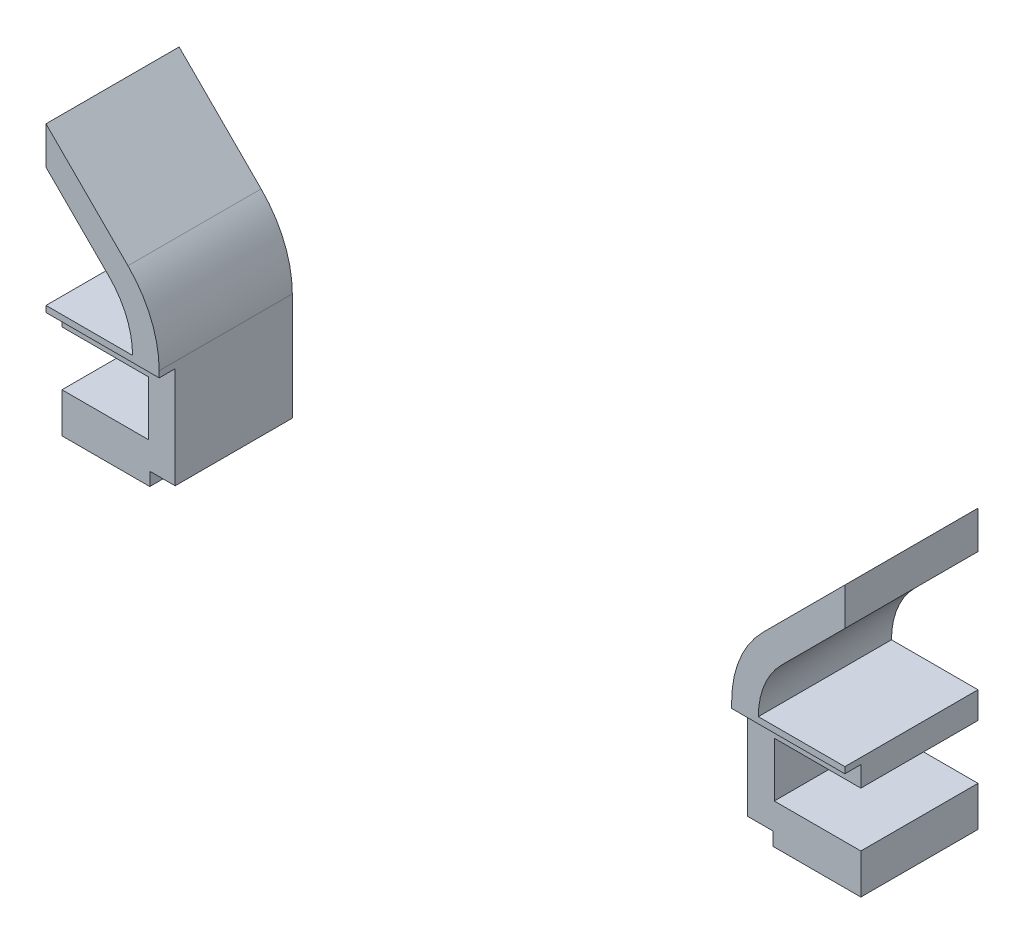
SolidWorks part; units mm, degrees
ref_plane "Front Plane" through (0, 0, 0) normal (0, 0, 1) x (1, 0, 0)
ref_plane "Top Plane" through (0, 0, 0) normal (0, 1, 0) x (1, 0, 0)
ref_plane "Right Plane" through (0, 0, 0) normal (1, 0, 0) x (0, 0, -1)
sketch "Sketch1" plane through (0, 0, 0) normal (0, 0, 1) x (1, 0, 0)
  line L0 (300, 74) -> (238.4315, 12.4315) construction
  line L2 (300, 74) -> (238.4315, 12.4315)
  line L4 (234.05, -125) -> (215, -125) construction
  line L5 (234.05, -125) -> (215, -125)
  line L6 (234.05, -125) -> (300, -125)
  line L7 (300, 300) -> (300, -300) construction
  line L8 (300, -125) -> (300, -105)
  line L9 (215, -125) -> (215, -105)
  line L10 (215, -105) -> (215, -44.1371)
  line L11 (300, 74) -> (300, 45.7157)
  line L12 (235, -105) -> (235, -64.1371)
  line L13 (300, 45.7157) -> (252.5736, -1.7107)
  line L14 (235, -105) -> (300, -105)
  line L15 (235, -44.1371) -> (300, -44.1371)
  line L16 (235, -125) -> (235, -105) construction
  line L17 (314.1421, 59.8579) -> (252.5736, -1.7107) construction
  line L18 (300, -44.1371) -> (300, -64.1371)
  line L19 (300, -64.1371) -> (235, -64.1371)
  line L21 (235, -105) -> (235, -44.1371) construction
  arc A0 (238.4315, 12.4315) -> (215, -44.1371) centre (295, -44.1371) ccw construction
  arc A1 (238.4315, 12.4315) -> (215, -44.1371) centre (295, -44.1371) ccw
  arc A2 (252.5736, -1.7107) -> (235, -44.1371) centre (295, -44.1371) ccw
  dimension "D1" = 20
extrude "Boss-Extrude1" add sketch "Sketch1" along normal up to surface (100 mm away)
sketch "Sketch2" plane through (215, 0, 0) normal (-1, 0, 0) x (0, 0, 1)
  line L0 (88, -125) -> (100, -125) construction
  line L1 (88, -48.8) -> (88, -125) construction
  line L2 (100, -48.8) -> (88, -48.8) construction
  line L3 (88, -125) -> (100, -125)
  line L4 (88, -48.8) -> (88, -125)
  line L5 (100, -48.8) -> (88, -48.8)
  line L6 (100, -48.8) -> (100, -125)
extrude "Cut-Extrude1" cut sketch "Sketch2" against normal through all
sketch "Sketch3" plane through (0, -125, 0) normal (0, -1, 0) x (1, 0, 0)
  line L1 (215, 0) -> (300, 0) construction
  line L2 (234.05, 0) -> (234.05, 88)
  line L3 (300, 88) -> (215, 88) construction
  line L4 (234.05, 88) -> (300, 88)
  line L5 (300, 88) -> (300, 0)
  line L6 (300, 0) -> (234.05, 0)
extrude "Boss-Extrude2" add sketch "Sketch3" along normal blind 10
mirror "Mirror1" about plane through (0, 0, 0) normal (1, 0, 0) of bodies 103
